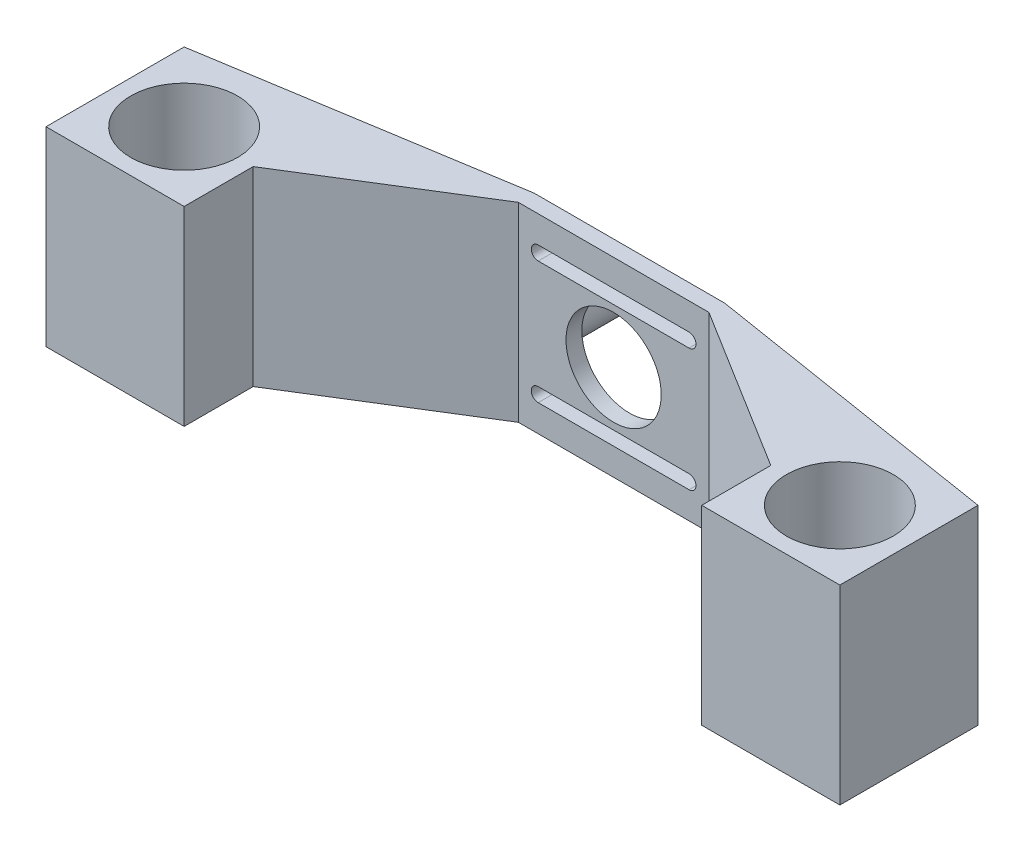
SolidWorks part; units mm, degrees
ref_plane "Front Plane" through (0, 0, 0) normal (0, 0, 1) x (1, 0, 0)
ref_plane "Top Plane" through (0, 0, 0) normal (0, 1, 0) x (1, 0, 0)
ref_plane "Right Plane" through (0, 0, 0) normal (1, 0, 0) x (0, 0, -1)
sketch "Sketch2" plane through (0, 0, 0) normal (0, 1, 0) x (1, 0, 0)
  line L0 (-17.4, -17.4) -> (82.6, -17.4) construction
  line L1 (-17.4, -17.4) -> (17.4, -17.4)
  line L2 (-17.4, -17.4) -> (-17.4, 17.4)
  line L5 (0, 17.4) -> (0, -17.4) construction
  line L6 (-17.4, 0) -> (17.4, 0) construction
  line L7 (82.6, -17.4) -> (82.6, 29.6) construction
  line L8 (17.4, -17.4) -> (17.4, 0)
  line L9 (82.6, 29.6) -> (58.6, 29.6)
  line L10 (82.6, 29.6) -> (82.6, 25.6)
  line L11 (82.6, 25.6) -> (58.6, 25.6)
  line L13 (17.4, 0) -> (58.6, 25.6)
  line L14 (58.6, 29.6) -> (-17.4, 17.4)
  circle A0 centre (0, 0) radius 13.45
  point P0 (0, 0)
  dimension "D3" = 26.9
  dimension "D8" = 17.4
  dimension "D9" = 17.4
  dimension "D1" = 34.8
  dimension "D2" = 34.8
  dimension "D4" = 100
  dimension "D5" = 47
  dimension "D6" = 24
  dimension "D7" = 4
extrude "Boss-Extrude1" add sketch "Sketch2" along normal blind 48
sketch3d "3DSketch1"
  line L0 (82.6, 0, -29.6) -> (82.6, 0, -25.6) construction
  line L1 (82.6, 0, -25.6) -> (82.6, 48, -25.6) construction
ref_plane "Plane1" through (82.6, 0, 0) normal (1, 0, 0) x (0, 0, -1)
mirror "Mirror1" about plane through (82.6, 0, 0) normal (1, 0, 0) of "Boss-Extrude1"
sketch "Sketch4" plane through (0, 0, -29.6) normal (0, 0, -1) x (-1, 0, 0)
  line L0 (-106.6, 24) -> (-58.6, 24) construction
  line L1 (-58.6, 48) -> (-58.6, 0) construction
  line L2 (-101.6, 8.55) -> (-63.6, 8.55) construction
  line L3 (-101.6, 10.3) -> (-63.6, 10.3)
  line L4 (-82.6, 0) -> (-82.6, 48) construction
  line L5 (-101.6, 6.8) -> (-63.6, 6.8)
  line L6 (-101.6, 39.45) -> (-63.6, 39.45) construction
  line L7 (-101.6, 37.7) -> (-63.6, 37.7)
  line L8 (-101.6, 41.2) -> (-63.6, 41.2)
  arc A0 (-101.6, 10.3) -> (-101.6, 6.8) centre (-101.6, 8.55) ccw
  arc A1 (-63.6, 6.8) -> (-63.6, 10.3) centre (-63.6, 8.55) ccw
  arc A2 (-101.6, 37.7) -> (-101.6, 41.2) centre (-101.6, 39.45) cw
  arc A3 (-63.6, 41.2) -> (-63.6, 37.7) centre (-63.6, 39.45) cw
  circle A4 centre (-82.6, 24) radius 12
  point P5 (-82.6, 24)
  point P7 (-82.6, 8.55)
  point P17 (-82.6, 39.45)
  dimension "D4" = 24
  dimension "D1" = 15.45
  dimension "D2" = 1.75
  dimension "D3" = 38
extrude "Cut-Extrude1" cut sketch "Sketch4" against normal blind 48
ref_plane "Plane2" through (0, 0, -29.6) normal (0, 0, -1) x (-1, 0, 0)
sketch "Sketch5" plane through (0, 0, -29.6) normal (0, 0, -1) x (-1, 0, 0)
  line L0 (-82.6, 24) -> (8.0606, 24) construction
  line L1 (-82.6, 0) -> (-82.6, 48) construction
  circle A2 centre (-62.1, 24) radius 4.1
  circle A3 centre (-62.1, 24) radius 7.1
  dimension "D1" = 8.2
  dimension "D3" = 3
  dimension "D2" = 20.5
extrude "Boss-Extrude2" add sketch "Sketch5" against normal blind 2
sketch "Sketch6" plane through (0, 0, -29.6) normal (0, 0, -1) x (-1, 0, 0)
  line L0 (-82.6, 24) -> (8.0606, 24) construction
  circle A2 centre (-62.1, 24) radius 4.1
  circle A3 centre (-62.1, 24) radius 7.1
  dimension "D1" = 8.2
  dimension "D3" = 3
  dimension "D2" = 20.5
extrude "Boss-Extrude3" add sketch "Sketch6" along normal blind 13
